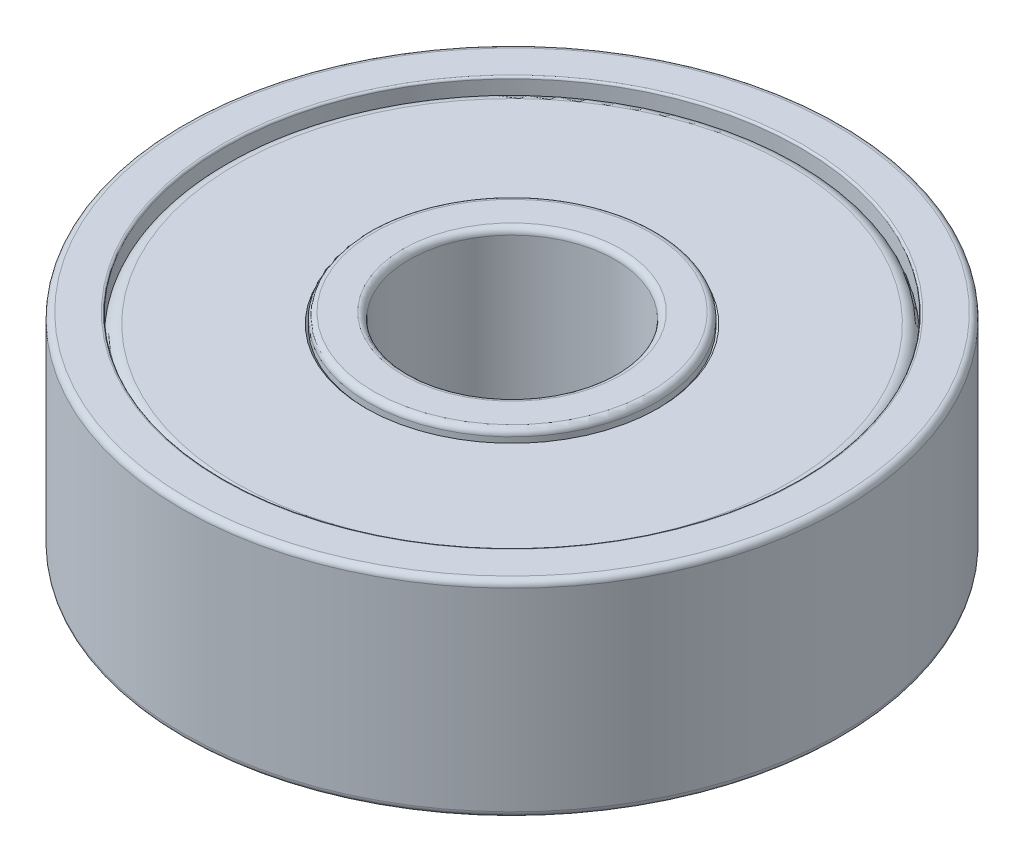
SolidWorks part; units mm, degrees
material "1060 Alloy"
ref_plane "Front Plane" through (0, 0, 0) normal (0, 0, 1) x (1, 0, 0)
ref_plane "Top Plane" through (0, 0, 0) normal (0, 1, 0) x (1, 0, 0)
ref_plane "Right Plane" through (0, 0, 0) normal (1, 0, 0) x (0, 0, -1)
sketch "Sketch1" plane through (0, 0, 0) normal (0, 1, 0) x (1, 0, 0)
  circle A0 centre (0, 0) radius 8
  circle A1 centre (0, 0) radius 7
  circle A2 centre (0, 0) radius 2.5
  circle A3 centre (0, 0) radius 3.5
  dimension "D1" = 16
  dimension "D2" = 1
  dimension "D3" = 5
  dimension "D4" = 1
extrude "Boss-Extrude1" add sketch "Sketch1" along normal mid plane 5 contours A0 A1 | A3 A2 region at (-7.7737, 0, 0) region at (-3.401, 0, 0)
fillet "Fillet1" radius 0.15 4 edges at (0, -2.5, 2.5) (0, 2.5, 2.5) (0, -2.5, 3.5) (0, 2.5, 3.5)
fillet "Fillet2" radius 0.15 2 edges at (0, -2.5, 8) (0, 2.5, 8)
fillet "Fillet3" radius 0.05 2 edges at (0, -2.5, 7) (0, 2.5, 7)
sketch "Sketch2" plane through (0, 0, 0) normal (0, 1, 0) x (1, 0, 0)
  circle A0 centre (0, 0) radius 7
  circle A1 centre (0, 0) radius 3.5
  circle A2 centre (0, 0) radius 7 construction
  circle A3 centre (0, 0) radius 3.5 construction
extrude "Boss-Extrude2" add sketch "Sketch2" along normal mid plane 4.5 separate body
fillet "Fillet4" radius 0.3 2 edges at (0, -2.25, 7) (0, 2.25, 7)
chamfer "Chamfer1" distance 0.05 angle 45 2 edges at (0, -2.25, 3.5) (0, 2.25, 3.5)
